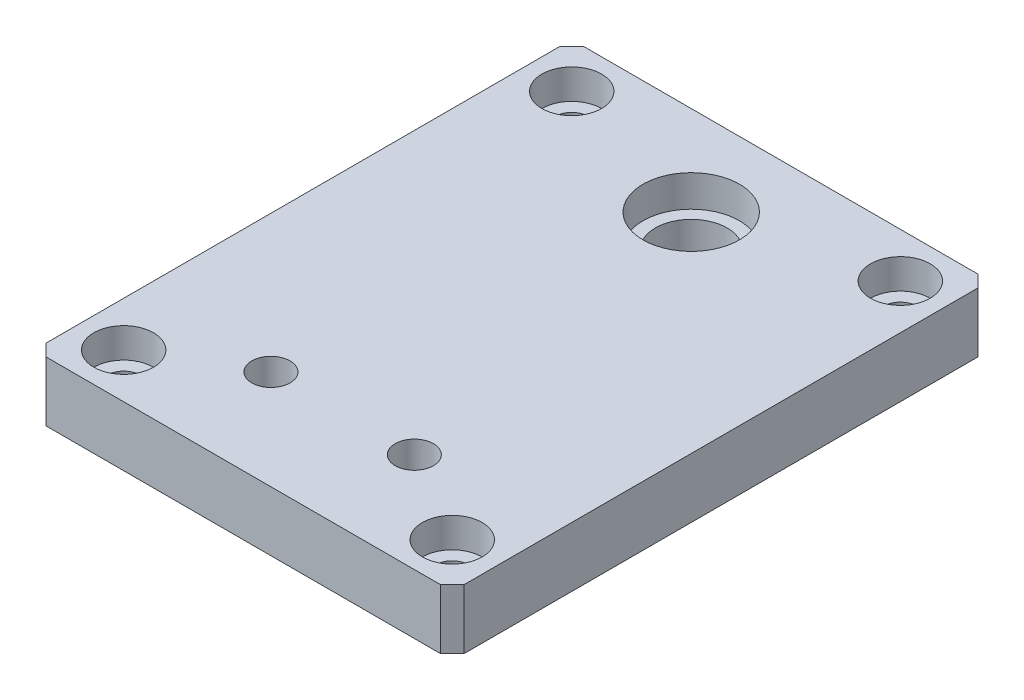
SolidWorks part; units mm, degrees
material "PET"
ref_plane "Front Plane" through (0, 0, 0) normal (0, 0, 1) x (1, 0, 0)
ref_plane "Top Plane" through (0, 0, 0) normal (0, 1, 0) x (1, 0, 0)
ref_plane "Right Plane" through (0, 0, 0) normal (1, 0, 0) x (0, 0, -1)
sketch "Sketch1" plane through (0, 0, 0) normal (0, 1, 0) x (1, 0, 0)
  line L1 (-35, -45) -> (35, -45)
  line L2 (-35, -45) -> (-35, 45)
  line L3 (-35, 45) -> (35, 45)
  line L4 (35, -45) -> (35, 45)
  line L5 (-35, -45) -> (35, 45) construction
  line L6 (-35, 45) -> (35, -45) construction
  point P0 (0, 0)
  dimension "D1" = 70
  dimension "D2" = 90
extrude "Boss-Extrude1" add sketch "Sketch1" along normal blind 10
sketch "Sketch4" plane through (0, 10, 0) normal (0, 1, 0) x (1, 0, 0)
  line L0 (-35, 45) -> (-35, -45) construction
  line L1 (35, 45) -> (-35, 45) construction
  line L3 (35, -45) -> (35, 45) construction
  line L4 (-35, -45) -> (35, -45) construction
  point P0 (-27.5, -37.5)
  point P2 (-27.5, 37.5)
  point P4 (27.5, 37.5)
  point P6 (27.5, -37.5)
  dimension "D1" = 7.5
  dimension "D2" = 7.5
  dimension "D3" = 7.5
  dimension "D4" = 7.5
hole_wizard "CBORE for M5 SHCS1" positions "Sketch4" profile "Sketch3" counterbore size "M5" standard "ANSI Metric" end condition through all
sketch "Sketch3" plane through (-27.5, 10, 37.5) normal (1, 0, 0) x (0, 0, 1)
  line L0 (0, 0) -> (0, 10)
  line L1 (0, 10) -> (2.75, 10)
  line L3 (2.75, 10) -> (2.75, 5)
  line L4 (2.75, 5) -> (5, 5)
  line L5 (5, 5) -> (5, 0)
  line L7 (5, 0) -> (0, 0)
  line L11 (0, -6.35) -> (0, 107.95) construction
  dimension "Thru Hole Dia." = 5.5
  dimension "Thru Hole Depth" = 10
  dimension "C'Bore Dia." = 10
  dimension "C'Bore Depth" = 5
sketch "Sketch7" plane through (0, 10, 0) normal (0, 1, 0) x (1, 0, 0)
  line L0 (35, 45) -> (-35, 45) construction
  point P0 (0, 30)
  dimension "D1" = 15
hole_wizard "Ø1.0mm Dowel Hole1" positions "Sketch7" profile "Sketch6" hole size "Ø1.0" standard "ANSI Metric"
sketch "Sketch6" plane through (0, 10, -30) normal (1, 0, 0) x (0, 0, 1)
  line L0 (0, 0) -> (0, 5.3)
  line L1 (0, 5.3) -> (8.075, 5.3)
  line L2 (8.075, 5.3) -> (8.075, 0)
  line L5 (8.075, 0) -> (0, 0)
  line L10 (0, 5.3) -> (-8.075, 5.3) construction
  line L11 (0, -6.35) -> (0, 107.95) construction
  dimension "Hole Dia." = 16.15
  dimension "Hole Depth" = 5.3
  dimension "Drill Angle" = 180
sketch "Sketch13" plane through (0, 4.7, 0) normal (0, 1, 0) x (1, 0, 0)
  point P0 (0, 30)
hole_wizard "Ø1.0mm Dowel Hole3" positions "Sketch13" profile "Sketch12" hole size "Ø1.0" standard "ANSI Metric" end condition through all
sketch "Sketch12" plane through (0, 4.7, -30) normal (1, 0, 0) x (0, 0, 1)
  line L0 (0, 0) -> (0, 4.7)
  line L1 (0, 4.7) -> (6, 4.7)
  line L2 (6, 4.7) -> (6, 0)
  line L5 (6, 0) -> (0, 0)
  line L11 (0, -6.35) -> (0, 107.95) construction
  dimension "Thru Hole Dia." = 12
  dimension "Thru Hole Depth" = 4.7
sketch "Sketch14" plane through (0, 10, 0) normal (0, 1, 0) x (1, 0, 0)
  circle A2 centre (12, -28.35) radius 3.2
  circle A3 centre (-12, -28.35) radius 3.2
  dimension "D5" = 6.4
  dimension "D6" = 6.4
  dimension "D1" = 28.35
  dimension "D2" = 12
  dimension "D3" = 12
  dimension "D4" = 28.35
extrude "Cut-Extrude1" cut sketch "Sketch14" against normal through all
chamfer "Chamfer1" distance 2 angle 45 4 edges at (35, 5, 45) (35, 5, -45) (-35, 5, -45) (-35, 5, 45)
equation "\"D1@Sketch4\" = 5 * 1.5"
equation "\"D2@Sketch4\" = \"D1@Sketch4\""
equation "\"D4@Sketch14\"=\"D1@Sketch14\""
